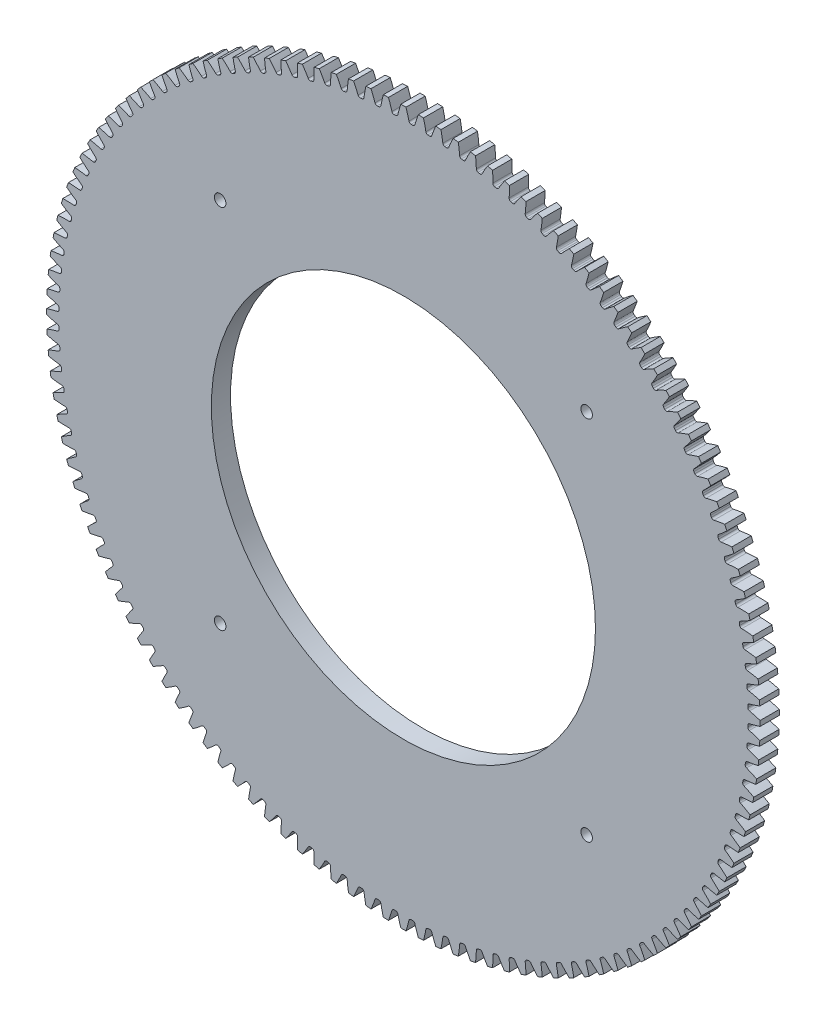
SolidWorks part; units mm, degrees
note: '?' marks a value the reader was unsure of.
ref_plane "Front" through (0, 0, 0) normal (0, 0, 1) x (1, 0, 0)
ref_plane "Top" through (0, 0, 0) normal (0, 1, 0) x (1, 0, 0)
ref_plane "Right" through (0, 0, 0) normal (1, 0, 0) x (0, 0, -1)
sketch "Sketch3" plane through (0, 0, 0) normal (0, 0, 1) x (1, 0, 0)
  circle A0 centre (0, 0) radius 117.9286
  dimension "od" = 235.8571
extrude "gearBody" add sketch "Sketch3" along normal blind 6.35
sketch "Sketch2" plane through (0, 0, 0) normal (0, 0, 1) x (1, 0, 0)
  line L0 (0, 0) -> (103.8586, 43.0197) construction
  line L1 (140.9141, -23.9968) -> (0, 0) construction
  line L2 (0, 0) -> (36.3143, 0) construction
  line L3 (116.1059, -1.3958) -> (116.0347, -4.2987) construction
  line L5 (116.0703, -2.8473) -> (0, 0) construction
  line L7 (0, 0) -> (112.4158, 0) construction
  arc A0 (112.3931, -2.2561) -> (112.3686, -3.2574) centre (0, 0) ccw construction
  arc A1 (117.9255, -0.8535) -> (117.8255, -4.9296) centre (0, 0) ccw construction
  arc A2 (116.1059, -1.3958) -> (116.0347, -4.2987) centre (0, 0) ccw construction
  arc A3 (113.845, -3.0682) -> (113.8585, -2.5175) centre (0, 0) ccw
  arc A4 (140.9141, -23.9968) -> (114.3697, -3.7851) centre (101.6244, -48.0603) ccw
  arc A5 (140.9141, -23.9968) -> (141.9212, 17.0587) centre (0, 0) ccw
  arc A6 (141.9212, 17.0587) -> (114.4177, -1.8272) centre (103.8586, 43.0197) cw
  arc A7 (113.8585, -2.5175) -> (114.4177, -1.8272) centre (114.5841, -2.5336) cw
  arc A8 (114.3697, -3.7851) -> (113.845, -3.0682) centre (114.5705, -3.0877) cw
  point P6 (141.9212, 17.0587)
  point P22 (140.9141, -23.9968)
  dimension "baseDia" = 224.8315
  dimension "od" = 235.8571
  dimension "pd" = 232.2286
  dimension "rd" = 227.7727
  dimension "rFillet" = 0.7257
  dimension "pointX" = 141.9212
  dimension "pointY" = 17.0587
  dimension "CTT" = 2.9029
  dimension "flankCenterAngle" = 22.5
extrude "toothCut" cut sketch "Sketch2" along normal through all
pattern_circular "CirPattern1" count 128 over 360 about axis through (0, 0, 0) along (0, 0, 1) of "toothCut"
ref_axis "toothSpace" through (0, 0, 0) along (0.9997, -0.0245, 0)?
ref_axis "Axis2" through (117.7866, -5.7844, 0) along (-0.9988, 0.049, 0)?
sketch "hub1Dia" plane through (0, 0, 0) normal (0, 0, -1) x (-1, 0, 0)
  circle A0 centre (0, 0) radius 12.7
  dimension "hub1Dia" = 25.4
sketch "hub2Dia" plane through (0, 0, 6.35) normal (0, 0, 1) x (1, 0, 0)
  circle A0 centre (0, 0) radius 12.7
  dimension "hub2dia" = 25.4
sketch "boreDia" plane through (0, 0, 0) normal (0, 0, 1) x (1, 0, 0)
  circle A0 centre (0, 0) radius 63.5
  circle A1 centre (60.579, 60.579) radius 1.905
  circle A2 centre (-60.579, 60.579) radius 1.905
  circle A3 centre (-60.579, -60.579) radius 1.905
  circle A4 centre (60.579, -60.579) radius 1.905
  point P13 (-174.6246, 10.4775)
  dimension "D1" = 3.81
  dimension "boreDia" = 127
  dimension "D2" = 3.81
  dimension "D3" = 3.81
  dimension "D4" = 3.81
  dimension "D5" = 60.579
  dimension "D6" = 60.579
  dimension "D7" = 60.579
  dimension "D8" = 60.579
  dimension "D9" = 121.158
  dimension "D10" = 121.158
  dimension "D11" = 60.579
  dimension "D12" = 121.158
extrude "bore" cut sketch "boreDia" against normal mid plane 25400
sketch "kwy1sketch" plane through (0, 0, 0) normal (0, 0, 1) x (1, 0, 0)
  line L0 (-5.9992, 0.2454) -> (0, 0) construction
  line L1 (28.3089, 11.5525) -> (27.2706, -13.8263)
  line L2 (27.2706, -13.8263) -> (-4.4528, -12.5285)
  line L3 (28.3089, 11.5525) -> (-3.4146, 12.8503)
  line L4 (-4.4528, -12.5285) -> (0, 0)
  line L5 (0, 0) -> (-3.4146, 12.8503)
  line L6 (0, 0) -> (113.8521, -2.7929) construction
  line L7 (27.7898, -1.1369) -> (0, 0) construction
  arc A7 (113.845, -3.0682) -> (113.8585, -2.5175) centre (0, 0) ccw construction
  point P9 (27.7898, -1.1369)
  point P13 (-1.0007, 0.0409)
  dimension "kwy1width" = 25.4
  dimension "kwy1depth" = 27.813
  dimension "kwy1angle" = 0.938
  dimension "kwy1Depth2" = 31.75
sketch "kwy2sketch" plane through (0, 0, 0) normal (0, 0, 1) x (1, 0, 0)
  line L0 (113.8521, -2.7929) -> (0, 0) construction
  line L1 (0, 0) -> (-3.0513, -2.8115) construction
  line L2 (11.8486, 28.1862) -> (29.0599, 9.5066)
  line L3 (29.0599, 9.5066) -> (5.7103, -12.0076)
  line L4 (11.8486, 28.1862) -> (-11.501, 6.6721)
  line L5 (5.7103, -12.0076) -> (0, 0)
  line L6 (0, 0) -> (-11.501, 6.6721)
  arc A2 (113.845, -3.0682) -> (113.8585, -2.5175) centre (0, 0) ccw construction
  point P10 (20.4542, 18.8464)
  dimension "kwy2angle" = 44.063
  dimension "kwy2Width" = 25.4
  dimension "kwy2depth" = 27.813
  dimension "kwy2Depth2" = 31.75
sketch "kwy3sketch" plane through (0, 0, 0) normal (0, 0, 1) x (1, 0, 0)
  line L0 (113.8521, -2.7929) -> (0, 0) construction
  line L1 (0, 0) -> (-0.1227, -2.9992) construction
  line L2 (-11.5525, 28.3089) -> (13.8263, 27.2706)
  line L3 (13.8263, 27.2706) -> (12.5285, -4.4528)
  line L4 (-11.5525, 28.3089) -> (-12.8503, -3.4146)
  line L5 (12.5285, -4.4528) -> (0, 0)
  line L6 (-12.8503, -3.4146) -> (0, 0)
  point P10 (1.1369, 27.7898)
  dimension "kwy3angle" = 89.063
  dimension "kwy3depth" = 27.813
  dimension "kwy3width" = 25.4
  dimension "kwy3Depth2" = 31.75
sketch "kwy4sketch" plane through (0, 0, 0) normal (0, 0, 1) x (1, 0, 0)
  line L0 (113.8521, -2.7929) -> (0, 0) construction
  line L1 (0, 0) -> (1.5904, -1.7261) construction
  line L2 (-9.5066, 29.0599) -> (-28.1862, 11.8486)
  line L3 (-28.1862, 11.8486) -> (-6.6721, -11.501)
  line L4 (-6.6721, -11.501) -> (0, 0)
  line L5 (12.0076, 5.7103) -> (0, 0)
  line L6 (-9.5066, 29.0599) -> (12.0076, 5.7103)
  point P15 (-18.8464, 20.4542)
  dimension "kwy4angle" = 134.063
  dimension "kwy4depth" = 27.813
  dimension "kwy4width" = 25.4
  dimension "kwy4Depth2" = 31.75
sketch "kwy5sketch" plane through (0, 0, 0) normal (0, 0, 1) x (1, 0, 0)
  line L0 (113.8521, -2.7929) -> (0, 0) construction
  line L1 (0, 0) -> (2.014, -0.0824) construction
  line L2 (-27.2706, 13.8263) -> (-28.3089, -11.5525)
  line L3 (-28.3089, -11.5525) -> (3.4146, -12.8503)
  line L4 (-27.2706, 13.8263) -> (4.4528, 12.5285)
  line L5 (3.4146, -12.8503) -> (0, 0)
  line L6 (4.4528, 12.5285) -> (0, 0)
  point P10 (-27.7898, 1.1369)
  dimension "kwy5width" = 25.4
  dimension "kwy5depth" = 27.813
  dimension "kwy5angle" = 179.063
  dimension "kwy5Depth2" = 31.75
sketch "kwy6sketch" plane through (0, 0, 0) normal (0, 0, 1) x (1, 0, 0)
  line L0 (113.8521, -2.7929) -> (0, 0) construction
  line L1 (0, 0) -> (1.4812, 1.3648) construction
  line L2 (-29.0599, -9.5066) -> (-11.8486, -28.1862)
  line L3 (-11.8486, -28.1862) -> (11.501, -6.6721)
  line L4 (-29.0599, -9.5066) -> (-5.7103, 12.0076)
  line L5 (11.501, -6.6721) -> (0, 0)
  line L6 (-5.7103, 12.0076) -> (0, 0)
  point P10 (-20.4542, -18.8464)
  dimension "kwy6angle" = 224.063
  dimension "kwy6width" = 25.4
  dimension "kwy6depth" = 27.813
  dimension "kwy6Depth2" = 31.75
sketch "kwy7sketch" plane through (0, 0, 0) normal (0, 0, 1) x (1, 0, 0)
  line L0 (113.8521, -2.7929) -> (0, 0) construction
  line L1 (0, 0) -> (0.0922, 2.2546) construction
  line L2 (-13.8263, -27.2706) -> (11.5525, -28.3089)
  line L3 (-13.8263, -27.2706) -> (-12.5285, 4.4528)
  line L4 (11.5525, -28.3089) -> (12.8503, 3.4146)
  line L5 (-12.5285, 4.4528) -> (0, 0)
  line L6 (12.8503, 3.4146) -> (0, 0)
  point P10 (-1.1369, -27.7898)
  dimension "kwy7angle" = 89.063
  dimension "kwy7width" = 25.4
  dimension "kwy7depth" = 27.813
  dimension "kwy7angle1" = 269.063
  dimension "kwy7Depth2" = 31.75
sketch "kwy8sketch" plane through (0, 0, 0) normal (0, 0, 1) x (1, 0, 0)
  line L0 (113.8521, -2.7929) -> (0, 0) construction
  line L1 (0, 0) -> (-1.3584, 1.4743) construction
  line L2 (9.5066, -29.0599) -> (28.1862, -11.8486)
  line L3 (28.1862, -11.8486) -> (6.6721, 11.501)
  line L4 (9.5066, -29.0599) -> (-12.0076, -5.7103)
  line L5 (6.6721, 11.501) -> (0, 0)
  line L6 (-12.0076, -5.7103) -> (0, 0)
  point P10 (18.8464, -20.4542)
  dimension "kwy8angle" = 314.063
  dimension "kwy8width" = 25.4
  dimension "kwy8depth" = 27.813
  dimension "kwy8Depth2" = 31.75
sketch "centerLine" plane through (0, 0, 0) normal (0, 1, 0) x (1, 0, 0)
  line L0 (0, 36.4807) -> (0, -59.6309) construction
ref_plane "CB1plane" through (0, 0, 0) normal (0, 0, -1) x (-1, 0, 0)
sketch "CB1diameter" plane through (0, 0, 0) normal (0, 0, -1) x (-1, 0, 0)
  circle A0 centre (0, 0) radius 12.7
  dimension "CB1diameter" = 25.4
ref_plane "CB2plane" through (0, 0, 6.35) normal (0, 0, 1) x (1, 0, 0)
sketch "CB2diameter" plane through (0, 0, 6.35) normal (0, 0, 1) x (1, 0, 0)
  circle A0 centre (0, 0) radius 12.7
  dimension "CB2diameter" = 25.4
ref_axis "Axis1" through (0, 0, 50) along (0, 0, -1)?
